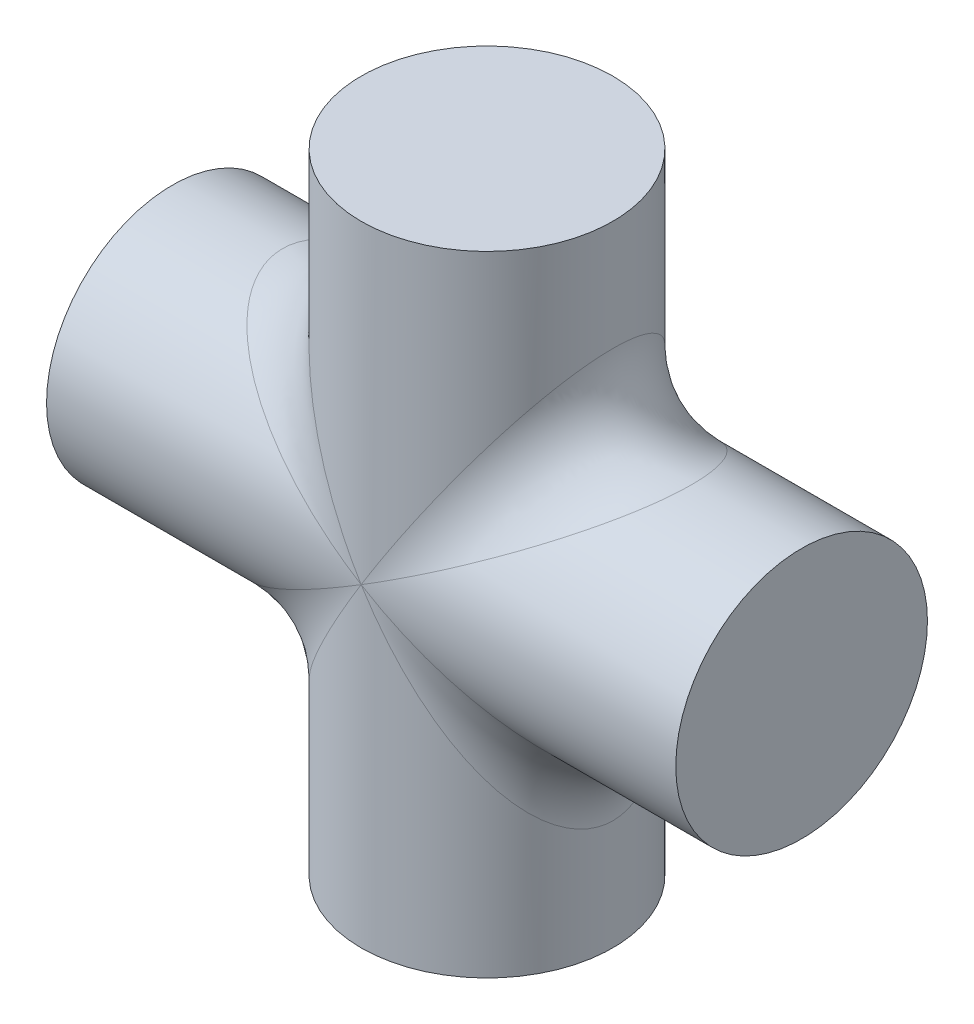
SolidWorks part; units mm, degrees
ref_plane "前视基准面" through (0, 0, 0) normal (0, 0, 1) x (1, 0, 0)
ref_plane "上视基准面" through (0, 0, 0) normal (0, 1, 0) x (1, 0, 0)
ref_plane "右视基准面" through (0, 0, 0) normal (1, 0, 0) x (0, 0, -1)
sketch "草图1" plane through (0, 0, 0) normal (0, 1, 0) x (1, 0, 0)
  circle A0 centre (0, 0) radius 8
extrude "凸台-拉伸1" add sketch "草图1" along normal mid plane 40
sketch "草图2" plane through (0, 0, 0) normal (1, 0, 0) x (0, 0, -1)
  circle A0 centre (0, 0) radius 8
extrude "凸台-拉伸2" add sketch "草图2" along normal mid plane 40
fillet "圆角1" radius 5 4 edges at (8, 8, 0) (8, -8, 0) (-8, -8, 0) (-8, 8, 0)
